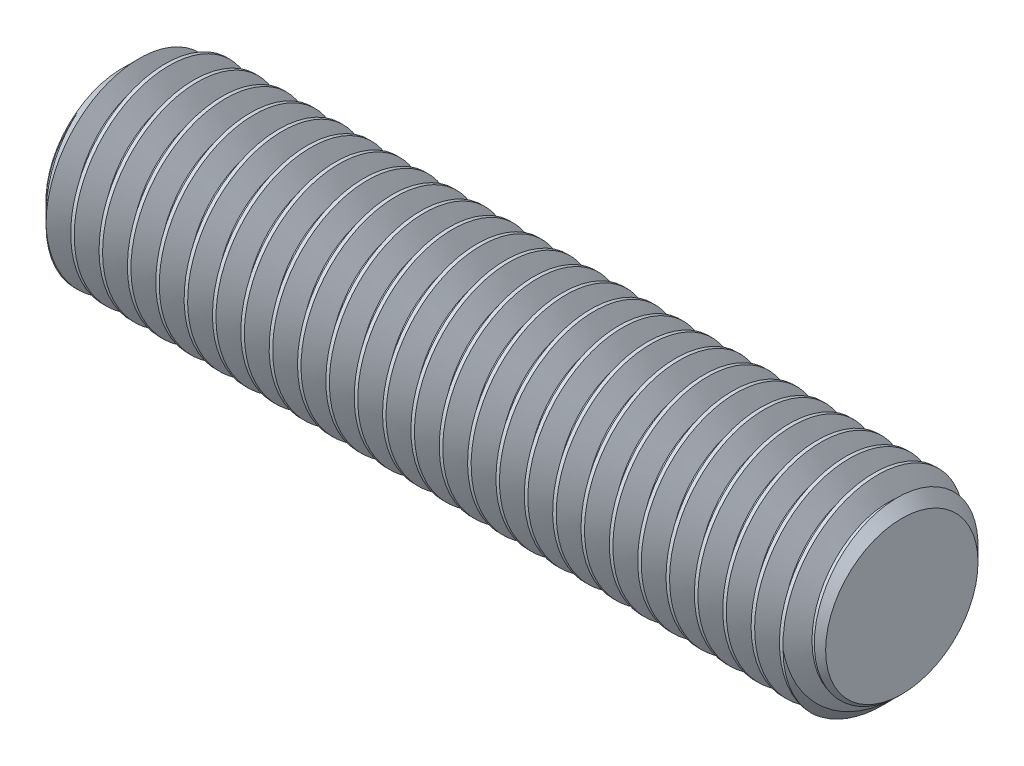
SolidWorks part; units mm, degrees
ref_plane "Front Plane" through (0, 0, 0) normal (0, 0, 1) x (1, 0, 0)
ref_plane "Top Plane" through (0, 0, 0) normal (0, 1, 0) x (1, 0, 0)
ref_plane "Right Plane" through (0, 0, 0) normal (1, 0, 0) x (0, 0, -1)
sketch "Sketch1" plane through (0, 0, 0) normal (0, 0, 1) x (1, 0, 0)
  line L0 (-31.75, 0) -> (31.75, 0) construction
  line L1 (31.75, 7.9375) -> (31.75, -7.9375) construction
  line L2 (-31.75, 7.9375) -> (-31.75, -7.9375) construction
  point P6 (23.6682, -7.9375)
  dimension "Thread Diameter" = 15.875
  dimension "Length" = 63.5
  dimension "D1" = 8.0818
sketch "Sketch2" plane through (0, 0, 0) normal (1, 0, 0) x (0, 0, -1)
  circle A0 centre (0, 0) radius 7.9375
extrude "Boss-Extrude1" add sketch "Sketch2" against normal up to vertex (31.75 mm away) and the other way up to vertex (31.75 mm away) up to point (-31.75, 0, 0) other way up to point (31.75, 0, 0)
sketch "Sketch3" plane through (31.75, 0, 0) normal (1, 0, 0) x (0, 0, -1)
  circle A1 centre (0, 0) radius 7.9375
  circle A2 centre (0, 0) radius 7.9375
  dimension "D1" = 0
curve "Helix/Spiral1" pitch 2.3091 height 65.8091 turns 28.5 parameters "Pitch"=2.3091
chamfer "Chamfer1" distance 1.7318 angle 45 2 edges at (-31.75, 0, -7.9375) (31.75, 0, -7.9375)
sketch "Sketch4" plane through (0, 0, 0) normal (0, 0, 1) x (1, 0, 0)
  line L0 (31.6057, 8.1875) -> (32.7602, 6.1877) construction
  line L1 (32.7602, 6.1877) -> (33.9148, 8.1875) construction
  line L2 (33.9148, 8.1875) -> (31.6057, 8.1875) construction
  line L3 (32.7602, 8.1875) -> (32.7602, 7.9375) construction
  line L4 (32.7602, 6.1877) -> (32.7602, 6.4377) construction
  line L5 (32.6159, 6.4377) -> (32.9045, 6.4377) construction
  line L6 (31.75, 7.9375) -> (33.7705, 7.9375) construction
  line L7 (32.6159, 6.4377) -> (31.6778, 8.0625)
  line L8 (32.6159, 6.4377) -> (32.9045, 6.4377)
  line L9 (31.6778, 8.0625) -> (33.8426, 8.0625)
  line L10 (33.8426, 8.0625) -> (32.9045, 6.4377)
  point P13 (32.7602, 8.0625)
  dimension "D2" = 0.2886
sweep "Cut-Sweep3" cut profiles "Sketch4" path "Helix/Spiral1" align with end faces yes
equation "\"D3@Helix/Spiral1\" = \"Length@Sketch1\"+\"Pitch@Helix/Spiral1\""
equation "\"D1@Chamfer1\" = \"Pitch@Helix/Spiral1\"*.75"
equation "\"D1@Sketch4\" = \"Pitch@Helix/Spiral1\""
equation "\"D2@Sketch4\" = \"D1@Sketch4\"/8"
equation "\"D1@Sketch1\" = \"Pitch@Helix/Spiral1\"*3.50"
